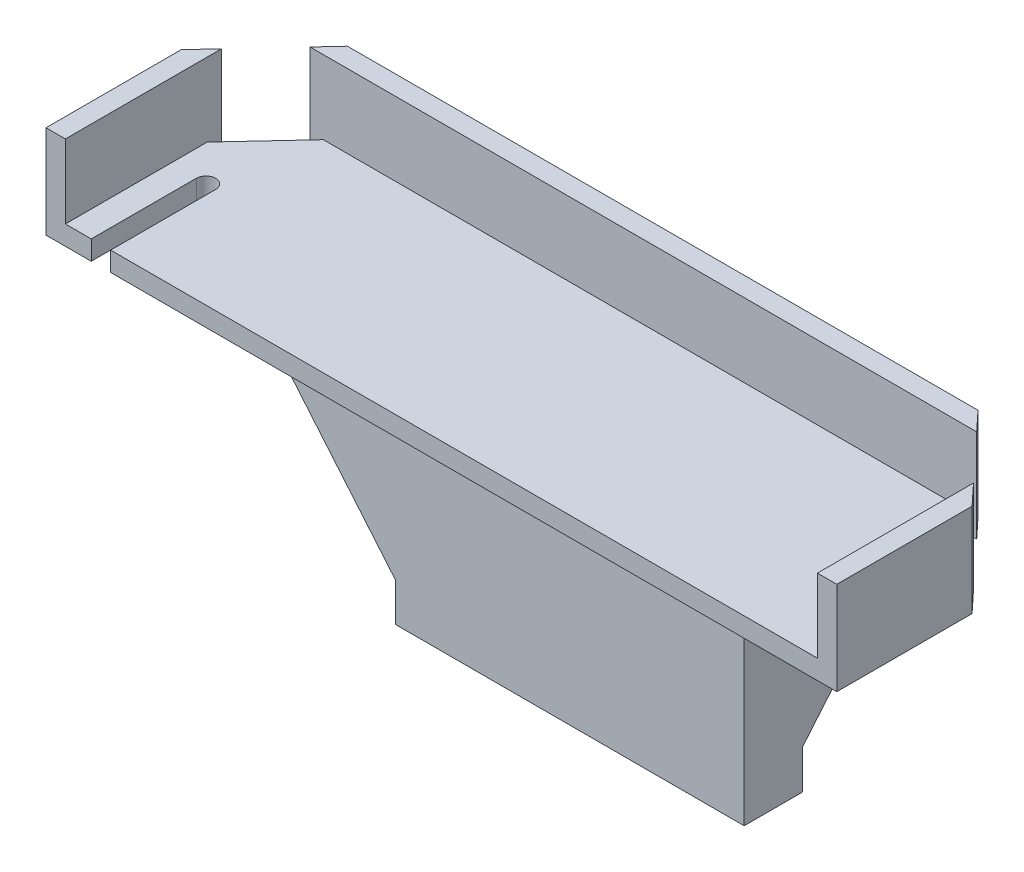
SolidWorks part; units mm, degrees
note: The reader was unsure of these and kept them because the rebuilt part matched: shared geometry of "Sketch5<3>".
ref_plane "Front Plane" through (0, 0, 0) normal (0, 0, 1) x (1, 0, 0)
ref_plane "Top Plane" through (0, 0, 0) normal (0, 1, 0) x (1, 0, 0)
ref_plane "Right Plane" through (0, 0, 0) normal (1, 0, 0) x (0, 0, -1)
sketch "Sketch1" plane through (0, 0, 0) normal (0, 1, 0) x (1, 0, 0)
  line L0 (-3, -1.5) -> (-3, 1.5)
  line L1 (-15, -1.5) -> (15, -1.5)
  line L2 (-15, -1.5) -> (-15, 1.5)
  line L3 (-15, 1.5) -> (15, 1.5)
  line L4 (15, -1.5) -> (15, 1.5)
  line L5 (-15, -1.5) -> (15, 1.5) construction
  line L6 (-15, 1.5) -> (15, -1.5) construction
  point P4 (0, 0)
  dimension "D1" = 30
  dimension "D2" = 3
  dimension "D3" = 12
extrude "Boss-Extrude1" add sketch "Sketch1" along normal blind 9 contours L1 L4 L3 L0
sketch "Sketch4" plane through (0, 9, 0) normal (0, 1, 0) x (1, 0, 0)
  line L0 (0, 9.3) -> (0, -4.6201) construction
  line L5 (-20.4, -4.6201) -> (17.9, -4.6201) construction
  line L7 (-16.2653, 9.3) -> (16.2653, 9.3)
  line L8 (-16.2653, 9.3) -> (-20.4, 4.858)
  line L9 (-20.4, 4.858) -> (-20.4, -4.6201)
  line L10 (-20.4, -4.6201) -> (20.4, -4.6201)
  line L15 (20.4, 4.858) -> (20.4, -4.6201)
  line L16 (16.2653, 9.3) -> (20.4, 4.858)
  point P7 (0, 1.8464)
  point P20 (0, -4.6201)
  dimension "D1" = 20.4
  dimension "D2" = 9.3
  dimension "D3" = 1.8464
  dimension "D4" = 6.4665
  dimension "D5" = 4.1347
  dimension "D6" = 4.442
  dimension "D7" = 4.6201
extrude "Boss-Extrude2" add sketch "Sketch4" along normal blind 4.8
sketch "Sketch5" plane through (0, 13.8, 0) normal (0, 1, 0) x (1, 0, 0)
  line L0 (0, -4.6201) -> (0, 9.3) construction
  line L1 (-20.4, -4.6201) -> (20.4, -4.6201) construction
  line L2 (16.2653, 9.3) -> (-16.2653, 9.3) construction
  line L3 (16.513, 8.3) -> (-16.513, 8.3)
  line L4 (-16.513, 8.3) -> (-19.4, 5.1985)
  line L5 (-19.4, 5.1985) -> (-19.4, -3.6201)
  line L6 (-19.4, -3.6201) -> (19.4, -3.6201)
  line L7 (-20.4, 4.858) -> (-20.4, -4.6201) construction
  line L8 (-16.2653, 9.3) -> (-20.4, 4.858) construction
  line L9 (19.4, 5.1985) -> (19.4, -3.6201)
  line L10 (16.513, 8.3) -> (19.4, 5.1985)
  line L11 (-19.4, -3.6201) -> (-20.4, -3.6201)
  line L12 (19.4, -3.6201) -> (20.4, -3.6201)
  line L13 (19.4, -3.6201) -> (20.4, -3.6201)
  point P17 (0, -3.6201)
  point P19 (0, 8.3)
  line M6 (-20.4, -4.6201) -> (20.4, -4.6201)
  line M7 (20.4, -4.6201) -> (20.4, 4.858)
  line M11 (-20.4, 4.858) -> (-20.4, -4.6201)
  dimension "D1" = 1
  dimension "D2" = 1
  dimension "D3" = 1
  dimension "D4" = 0.5
extrude "Cut-Extrude2" cut sketch "Sketch5" along direction (0, -1, 0) on the side against the normal offset from surface (3.8 mm away) 1 contours L0 L6 L9 L10 L3 | L6 L0 L3 L4 L5
extrude "Cut-Extrude3" cut sketch "Sketch5<3>" against normal blind 6 contours L0 L12 L6 M6 M7 | L0 L6 L11 M6 M11
sketch "Sketch5<3>" plane through (0, 13.8, 0) normal (0, 1, 0) x (1, 0, 0) same geometry as "Sketch5"
sketch "Sketch6" plane through (0, 13.8, 0) normal (0, 1, 0) x (1, 0, 0)
  line L0 (0, 0) -> (0, 13.98) construction
  line L1 (-19.4, 5.1985) -> (-19.4, 8.3)
  line L2 (-16.513, 8.3) -> (-19.4, 5.1985) construction
  line L3 (-19.4, 8.3) -> (-16.513, 8.3)
  line L4 (16.513, 8.3) -> (-16.513, 8.3) construction
  line L5 (-19.4, 5.1985) -> (-19.4, -3.6201) construction
  line L6 (-16.513, 8.3) -> (-19.4, 5.1985)
  line L7 (16.513, 8.3) -> (19.4, 5.1985)
  line L8 (19.4, 8.3) -> (16.513, 8.3)
  line L9 (19.4, 5.1985) -> (19.4, 8.3)
  dimension "D1" = 0
  dimension "D2" = 0
extrude "Cut-Extrude4" cut sketch "Sketch6" against normal blind 6.9
sketch "Sketch8" plane through (0, 10, 0) normal (0, 1, 0) x (1, 0, 0)
  line L0 (-17.5654, 3.3) -> (-17.5654, -4.9926) construction
  line L1 (-20.4, 4.858) -> (-20.4, -3.6201) construction
  line L2 (16.2653, 9.3) -> (-16.2653, 9.3) construction
  line L4 (-17.0654, 3.3) -> (-17.0654, -4.9926)
  line L5 (-18.0654, -4.9926) -> (-18.0654, 3.3)
  circle A0 centre (-17.5654, 3.3) radius 0.5 construction
  circle A1 centre (-17.5654, 0.76) radius 0.5 construction
  circle A2 centre (-17.5654, -1.78) radius 0.5 construction
  arc A4 (-18.0654, -4.9926) -> (-17.0654, -4.9926) centre (-17.5654, -4.9926) ccw
  arc A5 (-18.0654, 3.3) -> (-17.0654, 3.3) centre (-17.5654, 3.3) cw
  dimension "D4" = 1
  dimension "D5" = 2.8346
  dimension "D1" = 2.54
  dimension "D2" = 2.54
  dimension "D3" = 3.2126
  dimension "D6" = 6
extrude "Cut-Extrude5" cut sketch "Sketch8" against normal blind 4.5
sketch "Sketch9" plane through (0, 0, 0) normal (0, -1, 0) x (1, 0, 0)
  line L5 (-3, 1.5) -> (15, 1.5) construction
  line L10 (2.9155, 0) -> (5, 0) construction
  line L11 (5, 0) -> (7.0845, 0) construction
  circle A0 centre (2.9155, 0) radius 1
  circle A1 centre (7.0845, 0) radius 1
  point P4 (5, 0)
  dimension "D1" = 2
  dimension "D2" = 4.1691
  dimension "D3" = 1.5
  dimension "D4" = 5
extrude "Cut-Extrude6" cut sketch "Sketch9" against normal blind 4.5
sketch "Sketch12" plane through (0, 0, 3.6201) normal (0, 0, 1) x (1, 0, 0)
  line L1 (-20.4, 9) -> (20.4, 9)
  line L2 (-20.4, 9) -> (-20.4, 13.8)
  line L3 (-20.4, 13.8) -> (20.4, 13.8)
  line L4 (20.4, 9) -> (20.4, 13.8)
  line L5 (-20.4, 9) -> (20.4, 13.8) construction
  line L6 (-20.4, 13.8) -> (20.4, 9) construction
  point P4 (0, 11.4)
extrude "Cut-Extrude8" cut sketch "Sketch12" against normal blind 1.5
chamfer "Chamfer9" distance 7 angle 40 2 edges at (6, 9, -1.5) (-3, 9, 0)
